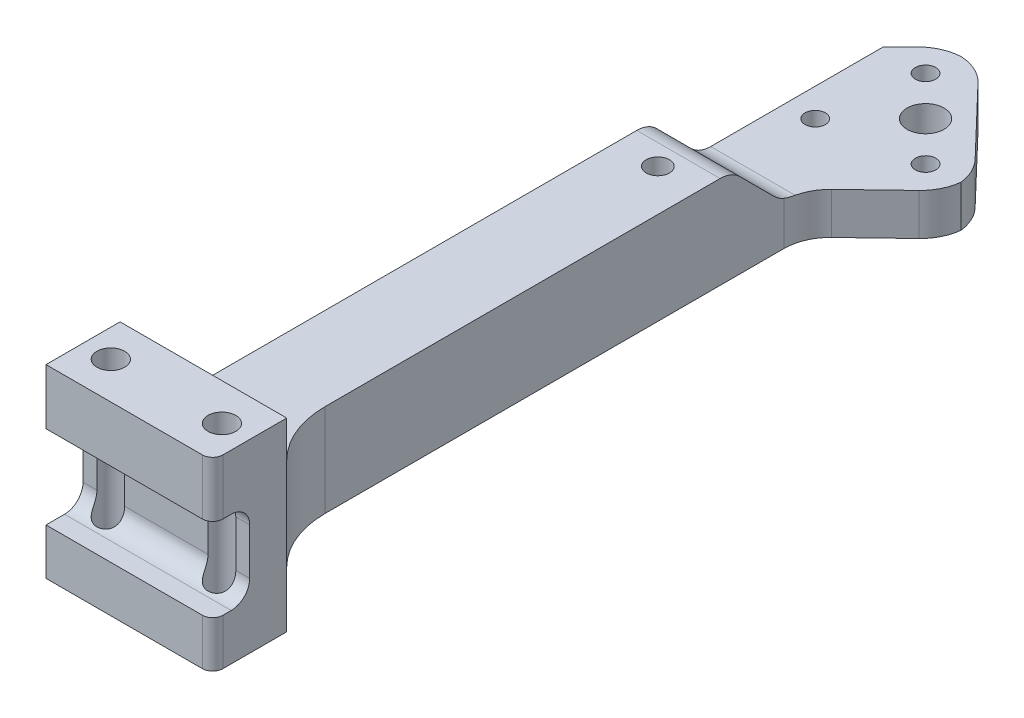
SolidWorks part; units mm, degrees
ref_plane "Front Plane" through (0, 0, 0) normal (0, 0, 1) x (1, 0, 0)
ref_plane "Top Plane" through (0, 0, 0) normal (0, 1, 0) x (1, 0, 0)
ref_plane "Right Plane" through (0, 0, 0) normal (1, 0, 0) x (0, 0, -1)
sketch "Sketch1" plane through (0, 0, 0) normal (0, 1, 0) x (1, 0, 0)
  line L0 (0, 90.435) -> (0, 0)
  line L1 (0, 0) -> (16.8886, 0)
  line L2 (18, 1.1114) -> (18, 8)
  line L3 (18, 8) -> (11.9289, 14.0711)
  line L4 (9, 21.1421) -> (9, 72.8487)
  line L5 (9, 72.8487) -> (9, 86) construction
  line L6 (3, 4) -> (15, 4) construction
  line L7 (0, 90.435) -> (3.3076, 93.7426)
  line L8 (3.3076, 93.7426) -> (6.9872, 93.7426)
  line L9 (6.9872, 93.7426) -> (16.8886, 83.4027)
  line L10 (16.8886, 83.4027) -> (16.8886, 80.4027)
  line L11 (16.8886, 80.4027) -> (9, 72.8487)
  line L12 (9, 86) -> (13.2426, 81.7574) construction
  line L13 (3.0415, 80.0415) -> (9, 86) construction
  line L14 (4.7574, 90.2426) -> (9, 86) construction
  circle A0 centre (9, 86) radius 6 construction
  circle A1 centre (9, 86) radius 8 construction
  circle A2 centre (3, 4) radius 1.5
  circle A3 centre (15, 4) radius 1.5
  arc A4 (16.8886, 0) -> (18, 1.1114) centre (16.8886, 1.1114) ccw
  circle A5 centre (13.2426, 81.7574) radius 1.1
  circle A6 centre (3.0415, 80.0415) radius 1.1
  circle A7 centre (4.7574, 90.2426) radius 1.1
  circle A8 centre (9, 86) radius 2
  arc A9 (11.9289, 14.0711) -> (9, 21.1421) centre (19, 21.1421) cw
  point P16 (18, 0)
  dimension "D7" = 9
  dimension "D8" = 3
  dimension "D10" = 12
  dimension "D11" = 16
  dimension "D16" = 4
  dimension "D22" = 2.2
  dimension "D23" = 10
  dimension "D2" = 8
  dimension "D3" = 12
  dimension "D4" = 4
  dimension "D5" = 3
  dimension "D6" = 45
  dimension "D9" = 82
  dimension "D12" = 45
  dimension "D13" = 90
  dimension "D14" = 90
  dimension "D15" = 3.5
  dimension "D17" = 3
  dimension "D18" = 3.5
  dimension "D19" = 45
  dimension "D20" = 3.5
  dimension "D21" = 4
  dimension "D24" = 18
extrude "Boss-Extrude1" add sketch "Sketch1" along normal blind 10
sketch "Sketch4" plane through (0, 10, 0) normal (0, 1, 0) x (1, 0, 0)
  line L0 (18, 8) -> (0, 8)
  line L1 (0, 90.435) -> (0, 0) construction
  line L2 (0, 8) -> (0, 0)
  line L3 (0, 0) -> (16.8886, 0)
  line L4 (18, 8) -> (18, 1.1114)
  line L15 (3.3076, 93.7426) -> (0, 90.435)
  line L16 (0, 90.435) -> (0, 0)
  line L17 (0, 0) -> (16.8886, 0)
  line L18 (18, 1.1114) -> (18, 8)
  line L19 (18, 8) -> (11.9289, 14.0711)
  line L20 (9, 21.1421) -> (9, 72.8487)
  line L21 (9, 72.8487) -> (16.8886, 80.4027)
  line L22 (16.8886, 80.4027) -> (16.8886, 83.4027)
  line L23 (16.8886, 83.4027) -> (6.9872, 93.7426)
  line L24 (6.9872, 93.7426) -> (3.3076, 93.7426)
  line L25 (3.3076, 93.7426) -> (0, 90.435)
  line L26 (0, 90.435) -> (0, 0)
  line L27 (0, 0) -> (16.8886, 0)
  line L28 (18, 1.1114) -> (18, 8)
  line L29 (18, 8) -> (11.9289, 14.0711)
  line L30 (9, 21.1421) -> (9, 72.8487)
  line L31 (9, 72.8487) -> (16.8886, 80.4027)
  line L32 (16.8886, 80.4027) -> (16.8886, 83.4027)
  line L33 (16.8886, 83.4027) -> (6.9872, 93.7426)
  line L34 (6.9872, 93.7426) -> (3.3076, 93.7426)
  arc A5 (16.8886, 0) -> (18, 1.1114) centre (16.8886, 1.1114) ccw
  arc A6 (9, 21.1421) -> (11.9289, 14.0711) centre (19, 21.1421) ccw
  arc A8 (9, 21.1421) -> (11.9289, 14.0711) centre (19, 21.1421) ccw
  line M2 (0, 90.435) -> (0, 0)
  line M3 (0, 0) -> (16.8886, 0)
  arc M4 (16.8886, 0) -> (18, 1.1114) centre (16.8886, 1.1114) ccw
  line M5 (18, 1.1114) -> (18, 8)
  circle M13 centre (3, 4) radius 1.5
  circle M14 centre (15, 4) radius 1.5
  dimension "D1" = 0
extrude "Boss-Extrude2" add sketch "Sketch4" along normal blind 10 contours L0 M5 M2 M3 M4 M14 M13 region at (8.9821, 10, -4.0077)
sketch "Sketch5" plane through (0, 0, 0) normal (-1, 0, 0) x (0, 0, 1)
  line L0 (0, 20) -> (0, 0) construction
  line L1 (0, 14) -> (-4, 14)
  line L2 (0, 14) -> (0, 5)
  line L3 (0, 5) -> (-4, 5)
  line L4 (-4, 14) -> (-4, 5)
  line L5 (-8, 20) -> (0, 20) construction
  line L6 (-90.435, 0) -> (0, 0) construction
  dimension "D1" = 6
  dimension "D2" = 4
  dimension "D3" = 5
extrude "Cut-Extrude1" cut sketch "Sketch5" against normal through all
sketch "Sketch6" plane through (0, 0, 0) normal (-1, 0, 0) x (0, 0, 1)
  line L0 (-8, 20) -> (-18, 10)
  line L1 (-90.435, 10) -> (-8, 10) construction
  line L14 (0, 0) -> (0, 5)
  line L15 (0, 5) -> (-4, 5)
  line L16 (-4, 5) -> (-4, 14)
  line L17 (-4, 14) -> (0, 14)
  line L18 (0, 14) -> (0, 20)
  line L19 (0, 20) -> (-8, 20)
  line L20 (-8, 20) -> (-8, 10)
  line L21 (-8, 10) -> (-90.435, 10)
  line L22 (-90.435, 10) -> (-90.435, 0)
  line L23 (-90.435, 0) -> (0, 0)
  line L30 (-8, 20) -> (-8, 10)
  line L31 (-8, 10) -> (-18, 10)
  dimension "D1" = 45
  dimension "D2" = 0
extrude "Boss-Extrude3" add sketch "Sketch6" against normal blind 10
sketch "Sketch7" plane through (0, 0, 0) normal (-1, 0, 0) x (0, 0, 1)
  line L0 (-93.7426, 4.5) -> (-70.5526, 4.5)
  line L1 (-93.7426, 10) -> (-93.7426, 0) construction
  line L2 (-70.5526, 4.5) -> (-65.0526, 10)
  line L3 (-90.435, 10) -> (-18, 10) construction
  line L4 (-65.0526, 10) -> (-93.7426, 10)
  line L5 (-93.7426, 10) -> (-93.7426, 4.5)
  line L6 (-93.7426, 0) -> (-90.435, 0) construction
  dimension "D1" = 4.5
  dimension "D2" = 45
  dimension "D3" = 23.19
extrude "Cut-Extrude2" cut sketch "Sketch7" against normal through all
fillet "Fillet1" radius 2 2 edges at (9, 5, -4) (9, 14, -4)
chamfer "Chamfer1" distance 7 angle 45 1 edges at (10, 15, -13)
fillet "Fillet2" radius 2 3 edges at (14, 10, -8) (6.5, 10, -13.0503) (6.5, 15.0503, -8)
fillet "Fillet3" radius 3 2 edges at (4.5, 4.5, -70.5526) (4.5, 10, -65.0526)
fillet "Fillet4" radius 5 5 edges at (9, 2.25, -72.8487) (16.8886, 2.25, -83.4027) (16.8886, 2.25, -80.4027) (6.9872, 2.25, -93.7426) (3.3076, 2.25, -93.7426)
sketch "Sketch8" plane through (0, 0, 0) normal (0, -1, 0) x (-1, 0, 0)
  line L0 (0, 90.435) -> (0, 0) construction
  circle A0 centre (-4.5, 61.5857) radius 1.25
  dimension "D2" = 2.5
  dimension "D1" = 4.5
  dimension "D3" = 32.15
extrude "Cut-Extrude3" cut sketch "Sketch8" against normal through all
